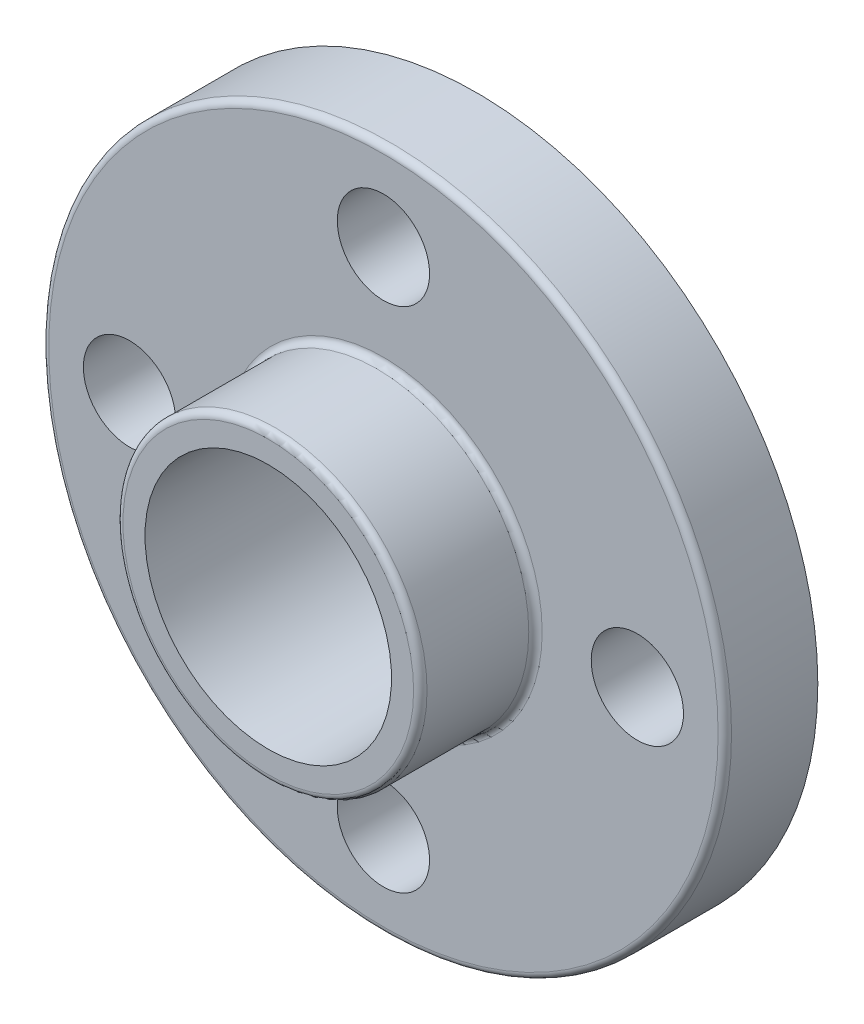
SolidWorks part; units mm, degrees
material "PVC"
ref_plane "Front Plane" through (0, 0, 0) normal (0, 0, 1) x (1, 0, 0)
ref_plane "Top Plane" through (0, 0, 0) normal (0, 1, 0) x (1, 0, 0)
ref_plane "Right Plane" through (0, 0, 0) normal (1, 0, 0) x (0, 0, -1)
sketch "Sketch0" plane through (0, 0, 0) normal (1, 0, 0) x (0, 0, -1)
  line L0 (0, 0) -> (-35.814, 0) construction
  point P3 (-16.002, 0)
  point P4 (-4.318, 0)
  dimension "Q" = 16.002
  dimension "C" = 35.814
  dimension "N" = 4.318
sketch "Sketch1" plane through (0, 0, 0) normal (0, 0, 1) x (1, 0, 0)
  circle A0 centre (0, 0) radius 58.7375
  circle A1 centre (0, 0) radius 21.209 construction
  circle A2 centre (0, 0) radius 43.688 construction
  circle A3 centre (0, 43.688) radius 7.9375 construction
  circle A4 centre (0, 0) radius 26.162 construction
  circle A5 centre (0, 0) radius 16.2306 construction
  circle A6 centre (0, 0) radius 21.0185 construction
  point P9 (0, 21.209)
  point P10 (0, 21.0185)
  point P11 (0, 16.2306)
  dimension "A" = 117.475
  dimension "B" = 87.376
  dimension "Bolt Hole Size" = 15.875
  dimension "Pipe OD A" = 42.418
  dimension "Hub OD" = 52.324
  dimension "Pipe ID" = 32.4612
  dimension "Pipe OD B" = 42.037
extrude "Extrude1" add sketch "Sketch1" along normal up to vertex (16.002 mm away) up to point (0, 0, 16.002)
sketch "Sketch2" plane through (0, 0, 16.002) normal (0, 0, 1) x (1, 0, 0)
  circle A0 centre (0, 0) radius 26.162 construction
  circle A1 centre (0, 0) radius 26.162
extrude "Extrude2" add sketch "Sketch2" along normal up to vertex (19.812 mm away) up to point (0, 0, 35.814)
sketch "Sketch3" plane through (0, 0, 16.002) normal (0, 0, 1) x (1, 0, 0)
  circle A0 centre (0, 43.688) radius 7.9375 construction
  circle A1 centre (0, 43.688) radius 7.9375
extrude "Extrude3" cut sketch "Sketch3" against normal through all
ref_axis "Axis1" through (0, 0, -1.7907) along (0, 0, 1)
pattern_circular "CirPattern1" count 4 over 360 about axis through (0, 0, -1.7907) along (0, 0, 1) of "Extrude3"
fillet "Fillet1" radius 1.1545 3 edges at (26.162, 0, 35.814) (26.162, 0, 16.002) (58.7375, 0, 16.002) tangent propagation no
sketch "Sketch4" plane through (0, 0, 63.5) normal (1, 0, 0) x (0, 0, -1)
  line L0 (27.686, 21.209) -> (59.182, 21.0185)
  line L1 (59.182, 21.0185) -> (59.182, 16.2306)
  line L2 (59.182, 16.2306) -> (63.5, 16.2306)
  line L3 (63.5, 16.2306) -> (63.5, 0)
  line L4 (63.5, 0) -> (27.686, 0)
  line L5 (27.686, 0) -> (27.686, 21.209)
  line L6 (63.5, 43.688) -> (63.5, -43.688) construction
  line L7 (59.182, 0) -> (59.182, 16.2306) construction
  line L8 (27.686, 21.209) -> (63.5, 21.209) construction
  line L12 (63.5, 21.0185) -> (59.182, 21.0185) construction
revolve "Cut-Revolve1" cut sketch "Sketch4" angle 360 about L4
